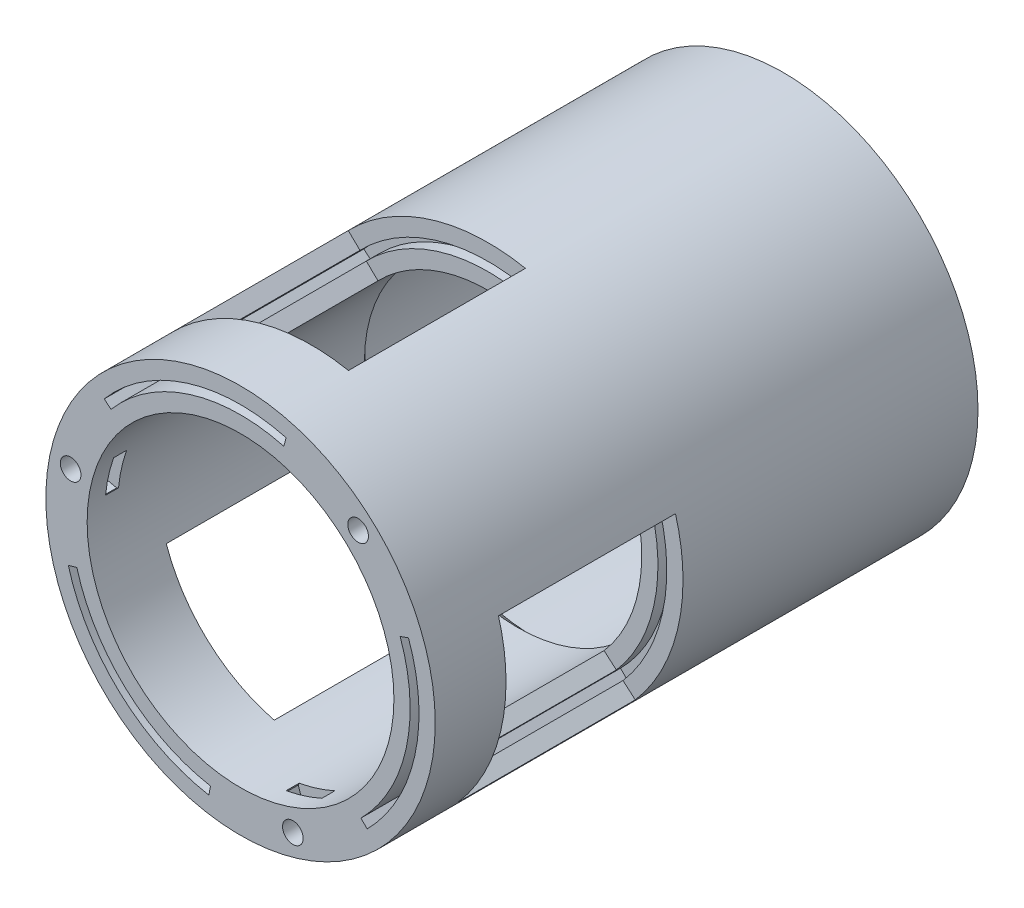
SolidWorks part; units mm, degrees
material "PEI"
ref_plane "Alzado" through (0, 0, 0) normal (0, 0, 1) x (1, 0, 0)
ref_plane "Planta" through (0, 0, 0) normal (0, 1, 0) x (1, 0, 0)
ref_plane "Vista lateral" through (0, 0, 0) normal (1, 0, 0) x (0, 0, -1)
sketch "Croquis1" plane through (0, 0, 0) normal (0, 0, 1) x (1, 0, 0)
  circle A0 centre (0, 0) radius 33
  circle A1 centre (0, 0) radius 29
  dimension "D1" = 66
  dimension "D2" = 4
extrude "Boss-Extrude1" add sketch "Croquis1" along normal blind 92
ref_axis "Eje1" through (0, 0, 92) along (0, 0, -1)
ref_plane "Plano2" through (0, 0, 0) normal (0.2756, -0.9613, 0) x (0, 0, -1)
sketch "Sketch8" plane through (0, 0, 0) normal (0, 0, -1) x (-1, 0, 0)
  arc A0 (-4, -28.7228) -> (4, -28.7228) centre (0, 0) ccw
  circle A1 centre (0, 0) radius 29 construction
  arc A2 (-4, -28.7228) -> (4, -28.7228) centre (0, -30.3008) cw
  arc A3 (-28.7228, 4) -> (-28.7228, -4) centre (0, 0) ccw
  arc A4 (-28.7228, 4) -> (-28.7228, -4) centre (-30.3008, 0) cw
  arc A5 (4, 28.7228) -> (-4, 28.7228) centre (0, 0) ccw
  arc A6 (4, 28.7228) -> (-4, 28.7228) centre (0, 30.3008) cw
  arc A7 (28.7228, -4) -> (28.7228, 4) centre (0, 0) ccw
  arc A8 (28.7228, -4) -> (28.7228, 4) centre (30.3008, 0) cw
  point P8 (0, -26.0008)
  point P20 (0, 0)
  dimension "D1" = 4.3
  dimension "D2" = 8
  dimension "D3" = 4
extrude "Boss-Extrude4" add sketch "Sketch8" against normal blind 15
sketch "Sketch9" plane through (0, 0, 0) normal (0, 0, -1) x (-1, 0, 0)
  circle A0 centre (0, -29) radius 1.75
  circle A1 centre (0, 0) radius 29 construction
  circle A2 centre (0, 0) radius 33 construction
  circle A3 centre (-29, 0) radius 1.75
  circle A4 centre (0, 29) radius 1.75
  circle A5 centre (29, 0) radius 1.75
  point P16 (0, 0)
  dimension "D1" = 4
  dimension "D2" = 3.5
  dimension "D3" = 4
extrude "Cut-Extrude3" cut sketch "Sketch9" against normal blind 14
ref_plane "Mid plane" through (0, 0, 46) normal (0, 0, 1) x (1, 0, 0)
ref_plane "Plano para USB y Switch" through (-23.3345, -23.3345, 0) normal (-0.7071, -0.7071, 0) x (0, 0, -1)
sketch "Sketch10" plane through (-23.3345, -23.3345, 0) normal (-0.7071, -0.7071, 0) x (0, 0, -1)
  line L0 (0, -33) -> (0, 33) construction
  line L1 (-10.5, 7.5) -> (-3.5, 7.5)
  line L2 (-10.5, 7.5) -> (-10.5, -7.5)
  line L3 (-10.5, -7.5) -> (-3.5, -7.5)
  line L4 (-3.5, 7.5) -> (-3.5, -7.5)
  line L5 (-10.5, 7.5) -> (-3.5, -7.5) construction
  line L6 (-10.5, -7.5) -> (-3.5, 7.5) construction
  line L8 (-45, 6.5) -> (-24, 6.5)
  line L9 (-45, 6.5) -> (-45, -6.5)
  line L10 (-45, -6.5) -> (-24, -6.5)
  line L11 (-24, 6.5) -> (-24, -6.5)
  line L12 (-45, 6.5) -> (-24, -6.5) construction
  line L13 (-45, -6.5) -> (-24, 6.5) construction
  point P0 (-7, 0)
  point P9 (-34.5, 0)
  dimension "D1" = 7
  dimension "D2" = 15
  dimension "D3" = 7
  dimension "D4" = 13
  dimension "D5" = 21
  dimension "D6" = 45
extrude "Corte USB y Switch" cut sketch "Sketch10" against normal blind 10
ref_plane "Plano USB PCB_C" through (12.362, 30.5971, 0) normal (0.3746, 0.9272, 0) x (0, 0, -1)
ref_plane "Plano tuercas superior" through (0, 0, 3) normal (0, 0, -1) x (-1, 0, 0)
sketch "Tuerca" plane through (0, 0, 3) normal (0, 0, -1) x (-1, 0, 0)
  line L30 (-29, -3.4064) -> (-25.5799, -3.4064)
  line L31 (-29, -3.4064) -> (-26.05, -1.7032) construction
  line L32 (-26.05, -1.7032) -> (-26.05, 1.7032) construction
  line L33 (-26.05, 1.7032) -> (-29, 3.4064) construction
  line L34 (-29, 3.4064) -> (-31.95, 1.7032)
  line L35 (-31.95, 1.7032) -> (-31.95, -1.7032)
  line L36 (-31.95, -1.7032) -> (-29, -3.4064)
  line L37 (-29, 3.4064) -> (-25.5799, 3.4064)
  circle A10 centre (-29, 0) radius 2.95 construction
  arc A12 (-25.5799, -3.4064) -> (-25.5799, 3.4064) centre (-28.2041, 0) ccw
  dimension "D4" = 5.9
extrude "Alojamiento tuerca" cut sketch "Tuerca" against normal blind 2.2 contours L30 A12 L37 L34 L35 L36 region at (27.8612, 0, 3)
pattern_circular "Alojamientos Tuercas Superior" count 4 over 360 about axis through (0, 0, 0) along (0, 0, 1) of "Alojamiento tuerca"
sketch "Sketch13" plane through (0, 0, 92) normal (0, 0, 1) x (1, 0, 0)
  circle A0 centre (0, 0) radius 29
  circle A1 centre (0, 0) radius 26
  circle A3 centre (0, 0) radius 29 construction
  circle A4 centre (0, 0) radius 33 construction
  dimension "D1" = 52
  dimension "D2" = 7
extrude "Grosor adicional" add sketch "Sketch13" against normal blind 47
sketch "Corte Revolucion" plane through (0, 0, 0) normal (0.2756, -0.9613, 0) x (0, 0, -1)
  line L0 (-80, 33) -> (-80, 25)
  line L2 (-80, 25) -> (-50, 25)
  line L4 (-50, 33) -> (-80, 33)
  line L5 (-97, 29) -> (-42, 29) construction
  line L6 (-92, 33) -> (-92, -33) construction
  line L14 (-50, 25) -> (-50, 33)
  dimension "D1" = 8
  dimension "D6" = 12
revolve "Cut-Revolve3" cut sketch "Corte Revolucion" angle 57 about axis through (0, 0, 92) along (0, 0, -1)
pattern_circular "CirPattern3" count 3 over 360 about axis through (0, 0, 0) along (0, 0, 1) of "Cut-Revolve3"
sketch "Croquis2" plane through (0, 0, 92) normal (0, 0, 1) x (1, 0, 0)
  line L0 (0, 0) -> (-23.101, 19.5296) construction
  line L1 (0, 0) -> (7.7215, 29.2479) construction
  line L2 (0, 0) -> (-21.76, 21.0134) construction
  line L3 (0, 0) -> (5.772, 29.6942) construction
  line L4 (7.7215, 29.2479) -> (7.3387, 27.7976)
  line L5 (-23.101, 19.5296) -> (-21.9555, 18.5612)
  line L6 (21.4687, -21.311) -> (20.4041, -20.2543)
  line L7 (28.4636, 10.2413) -> (27.0522, 9.7334)
  line L8 (6.2967, 32.3937) -> (4.961, 25.5223) construction
  line L9 (-23.7382, 22.9237) -> (-18.7028, 18.0611) construction
  line L10 (-29.1902, -7.9369) -> (-27.7428, -7.5433)
  line L11 (-5.3626, -29.7709) -> (-5.0967, -28.2946)
  circle A0 centre (0, 0) radius 28.75 construction
  circle A1 centre (0, 0) radius 30.25 construction
  arc A2 (28.4636, 10.2413) -> (21.4687, -21.311) centre (0, 0) cw
  circle A3 centre (0, 0) radius 29.5 construction
  arc A4 (-23.101, 19.5296) -> (7.7215, 29.2479) centre (0, 0) cw
  arc A5 (-21.9555, 18.5612) -> (7.3387, 27.7976) centre (0, 0) cw
  arc A6 (27.0522, 9.7334) -> (20.4041, -20.2543) centre (0, 0) cw
  arc A7 (-5.3626, -29.7709) -> (-29.1902, -7.9369) centre (0, 0) cw
  arc A8 (-5.0967, -28.2946) -> (-27.7428, -7.5433) centre (0, 0) cw
  circle A13 centre (0, 0) radius 33 construction
  circle A14 centre (0, 0) radius 26 construction
  point P4 (-22.5283, 19.0454)
  point P28 (0, 0)
  point P32 (0, 0)
  dimension "D1" = 1.5
  dimension "D2" = 7
  dimension "D6" = 3.5
  dimension "D3" = 2
  dimension "D4" = 2
  dimension "D5" = 3
extrude "Corte postizos" cut sketch "Croquis2" against normal offset from surface (44 mm away) 2 up to face at (-8.3333, 26.4299, 50) offset beyond the face yes
chamfer "Chamfer3" distance 3 angle 45 1 edges at (20.5061, 20.5061, 45)
sketch "Sketch14" plane through (0, 0, 92) normal (0, 0, 1) x (1, 0, 0)
  line L0 (7.3387, 27.7976) -> (0, 0) construction
  line L1 (0, 0) -> (27.0522, 9.7334) construction
  line L2 (0, 0) -> (19.9299, 21.7497) construction
  line L3 (28.4636, 10.2413) -> (27.0522, 9.7334) construction
  line L4 (7.7215, 29.2479) -> (7.3387, 27.7976) construction
  line L5 (0, 0) -> (8.8708, -28.1347) construction
  line L6 (0, 0) -> (-28.8007, 6.385) construction
  arc A0 (27.7579, 9.9874) -> (7.5301, 28.5228) centre (0, 0) ccw construction
  circle A1 centre (19.9299, 21.7497) radius 1.75
  circle A2 centre (8.8708, -28.1347) radius 1.75
  arc A3 (-5.2297, -29.0328) -> (20.9364, -20.7826) centre (0, 0) ccw construction
  circle A4 centre (-28.8007, 6.385) radius 1.75
  arc A5 (-22.5283, 19.0454) -> (-28.4665, -7.7401) centre (0, 0) ccw construction
  point P21 (15.6241, 4.4801)
  point P25 (0, 0)
  dimension "D3" = 3.5
  dimension "D1" = 55.422
  dimension "D2" = 27.711
  dimension "D4" = 3
extrude "Cut-Extrude6" cut sketch "Sketch14" against normal blind 17
ref_plane "Plano tuercas inferior" through (0, 0, 89) normal (0, 0, 1) x (1, 0, 0)
sketch "Sketch15" plane through (0, 0, 89) normal (0, 0, 1) x (1, 0, 0)
  line L0 (17.4155, 24.0477) -> (15.1082, 21.5231)
  line L1 (17.4155, 24.0477) -> (16.6825, 20.7211) construction
  line L2 (16.6825, 20.7211) -> (19.197, 18.4231) construction
  line L3 (19.197, 18.4231) -> (22.4444, 19.4517) construction
  line L4 (22.4444, 19.4517) -> (23.1773, 22.7783)
  line L5 (23.1773, 22.7783) -> (20.6628, 25.0763)
  line L6 (20.6628, 25.0763) -> (17.4155, 24.0477)
  line L7 (22.4444, 19.4517) -> (20.1371, 16.9271)
  line L8 (12.1182, -27.1061) -> (11.0855, -23.8456)
  line L9 (5.6235, -29.1632) -> (8.1379, -31.4612)
  line L10 (8.1379, -31.4612) -> (11.3853, -30.4327)
  line L11 (11.3853, -30.4327) -> (12.1182, -27.1061)
  line L12 (5.6235, -29.1632) -> (4.5907, -25.9027)
  line L13 (12.1182, -27.1061) -> (9.6037, -24.8081) construction
  line L14 (9.6037, -24.8081) -> (6.3564, -25.8366) construction
  line L15 (6.3564, -25.8366) -> (5.6235, -29.1632) construction
  line L16 (-29.5336, 3.0584) -> (-26.1936, 2.3225)
  line L17 (-28.0678, 9.7116) -> (-31.3152, 8.683)
  line L18 (-31.3152, 8.683) -> (-32.0481, 5.3564)
  line L19 (-32.0481, 5.3564) -> (-29.5336, 3.0584)
  line L20 (-28.0678, 9.7116) -> (-24.7278, 8.9757)
  line L21 (-29.5336, 3.0584) -> (-26.2863, 4.087) construction
  line L22 (-26.2863, 4.087) -> (-25.5534, 7.4135) construction
  line L23 (-25.5534, 7.4135) -> (-28.0678, 9.7116) construction
  circle A0 centre (19.9299, 21.7497) radius 2.95 construction
  arc A1 (15.1082, 21.5231) -> (20.1371, 16.9271) centre (19.393, 21.1622) ccw
  arc A2 (11.0855, -23.8456) -> (4.5907, -25.9027) centre (8.6305, -27.3759) ccw
  circle A3 centre (8.8708, -28.1347) radius 2.95 construction
  arc A5 (-26.1936, 2.3225) -> (-24.7278, 8.9757) centre (-28.0235, 6.2137) ccw
  circle A6 centre (-28.8007, 6.385) radius 2.95 construction
  point P38 (0, 0)
  dimension "D1" = 5.9
  dimension "D2" = 240
  dimension "D3" = 240
  dimension "D4" = 210
  dimension "D5" = 240
  dimension "D6" = 3.4201
  dimension "D7" = 3
extrude "Tuercas inferior" cut sketch "Sketch15" against normal blind 2.2
equation "\"D6@Croquis2\"=\"D2@Croquis2\"/2"
equation "\"D2@Sketch14\"=\"D1@Sketch14\"/2"
equation "\"D3@Sketch15\"=\"D2@Sketch15\""
equation "\"D5@Sketch15\"=\"D3@Sketch15\""
